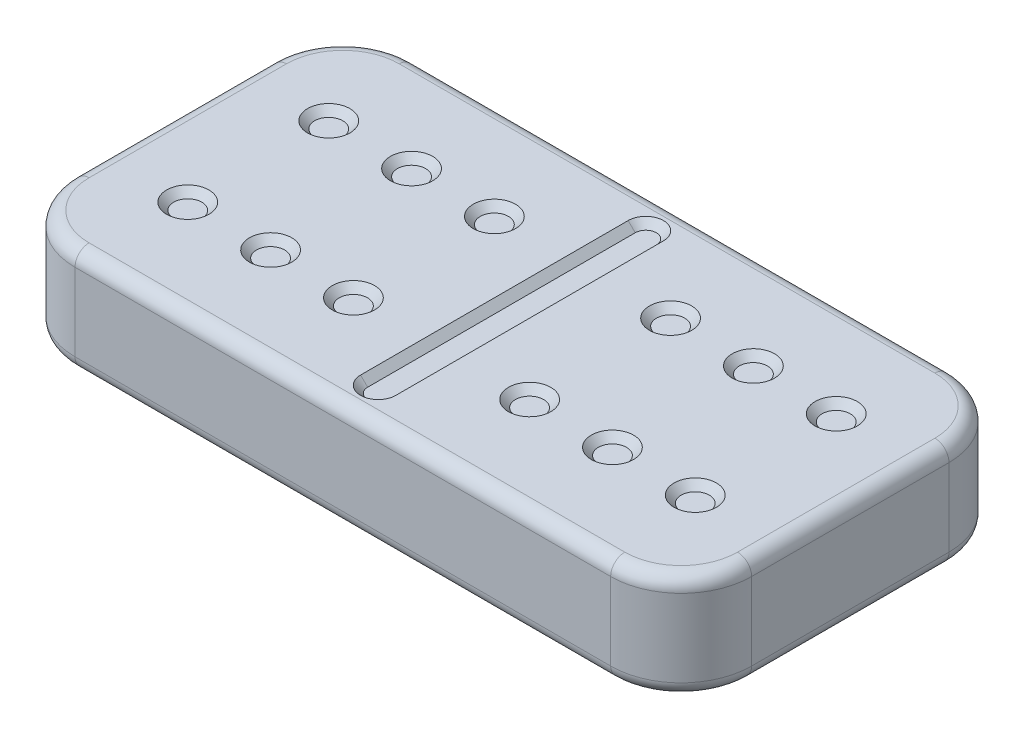
SolidWorks part; units mm, degrees
material "ABS"
ref_plane "Front Plane" through (0, 0, 0) normal (0, 0, 1) x (1, 0, 0)
ref_plane "Top Plane" through (0, 0, 0) normal (0, 1, 0) x (1, 0, 0)
ref_plane "Right Plane" through (0, 0, 0) normal (1, 0, 0) x (0, 0, -1)
sketch "Esquisse1" plane through (0, 0, 0) normal (0, 1, 0) x (1, 0, 0)
  line L1 (0, 0) -> (48, 0)
  line L2 (0, 0) -> (0, 24)
  line L3 (0, 24) -> (48, 24)
  line L4 (48, 0) -> (48, 24)
  dimension "D1" = 48
  dimension "D2" = 24
extrude "Extrusion1" add sketch "Esquisse1" along normal blind 7.5
fillet "Congé2" radius 5 4 edges at (48, 3.75, 0) (48, 3.75, -24) (0, 3.75, 0) (0, 3.75, -24)
fillet "Congé5" radius 1 8 edges at (46.5355, 7.5, -22.5355) (48, 7.5, -12) (46.5355, 7.5, -1.4645) (24, 7.5, 0) (1.4645, 7.5, -1.4645) (0, 7.5, -12) (1.4645, 7.5, -22.5355) (24, 7.5, -24)
fillet "Congé6" radius 1 8 edges at (46.5355, 0, -22.5355) (48, 0, -12) (46.5355, 0, -1.4645) (24, 0, 0) (1.4645, 0, -1.4645) (0, 0, -12) (1.4645, 0, -22.5355) (24, 0, -24)
sketch "Esquisse4" plane through (0, 7.5, 0) normal (0, 1, 0) x (1, 0, 0)
  line L0 (1, 12) -> (47, 12) construction
  line L1 (1, 19) -> (1, 5) construction
  line L2 (47, 5) -> (47, 19) construction
  line L3 (24, 23) -> (24, 1) construction
  line L4 (43, 23) -> (5, 23) construction
  line L5 (5, 1) -> (43, 1) construction
  line L7 (23.75, 21.4914) -> (24.25, 21.4914)
  line L8 (23.75, 21.4914) -> (23.75, 2.5086)
  line L9 (23.75, 2.5086) -> (24.25, 2.5086)
  line L10 (24.25, 21.4914) -> (24.25, 2.5086)
  line L11 (23.75, 21.4914) -> (24.25, 2.5086) construction
  line L12 (23.75, 2.5086) -> (24.25, 21.4914) construction
  point P12 (24, 12)
  dimension "D1" = 0.5
extrude "Extrusion2" cut sketch "Esquisse4" against normal blind 0.5
sketch "Esquisse5" plane through (0, 7.5, 0) normal (0, 1, 0) x (1, 0, 0)
  line L0 (24.25, 21.4914) -> (23.75, 21.4914) construction
  line L1 (23.75, 2.5086) -> (24.25, 2.5086) construction
  circle A0 centre (24, 21.4914) radius 0.25
  circle A1 centre (24, 2.5086) radius 0.25
  dimension "D1" = 0.5
  dimension "D2" = 0.5
extrude "Extrusion3" cut sketch "Esquisse5" against normal blind 0.5
chamfer "Chanfrein1" distance 1 angle 45 4 edges at (24, 7.5, -21.7414) (24.25, 7.5, -12) (24, 7.5, -2.2586) (23.75, 7.5, -12)
sketch "Esquisse6" plane through (0, 7.5, 0) normal (0, 1, 0) x (1, 0, 0)
  line L0 (1, 17) -> (22.75, 17) construction
  line L3 (47, 5) -> (47, 19) construction
  line L4 (25.25, 21.4914) -> (25.25, 2.5086) construction
  line L5 (1, 19) -> (1, 5) construction
  line L6 (1, 12) -> (1, 5) construction
  line L7 (1, 12) -> (1, 19) construction
  line L8 (1, 15.5) -> (1, 19) construction
  line L9 (1, 5) -> (1, 8.5) construction
  line L10 (22.75, 2.5086) -> (22.75, 21.4914) construction
  line L11 (1, 7) -> (22.75, 7) construction
  line L12 (6.4158, 23) -> (6.4158, 17) construction
  line L13 (43, 23) -> (5, 23) construction
  line L14 (6.4158, 7) -> (6.4158, 1) construction
  line L15 (5, 1) -> (43, 1) construction
  line L16 (11.875, 17) -> (6, 17) construction
  line L17 (11.875, 17) -> (11.875, 7) construction
  circle A0 centre (42, 17) radius 1.5
  circle A1 centre (36.125, 17) radius 1.5
  circle A2 centre (11.875, 17) radius 1.5
  circle A3 centre (17.75, 17) radius 1.5
  circle A4 centre (6, 17) radius 1.5
  circle A5 centre (11.875, 7) radius 1.5
  circle A6 centre (6, 7) radius 1.5
  circle A7 centre (17.75, 7) radius 1.5
  circle A8 centre (30.25, 17) radius 1.5
  circle A9 centre (30.25, 7) radius 1.5
  circle A10 centre (42, 7) radius 1.5
  circle A11 centre (36.125, 7) radius 1.5
  dimension "D1" = 3
  dimension "D5" = 5
  dimension "D2" = 6
  dimension "D3" = 6
  dimension "D4" = 90
  dimension "D6" = 5
  dimension "D7" = 5
  dimension "D8" = 5
  dimension "D9" = 5
  dimension "D10" = 5
extrude "Extrusion6" cut sketch "Esquisse6" against normal blind 0.5 draft 45
